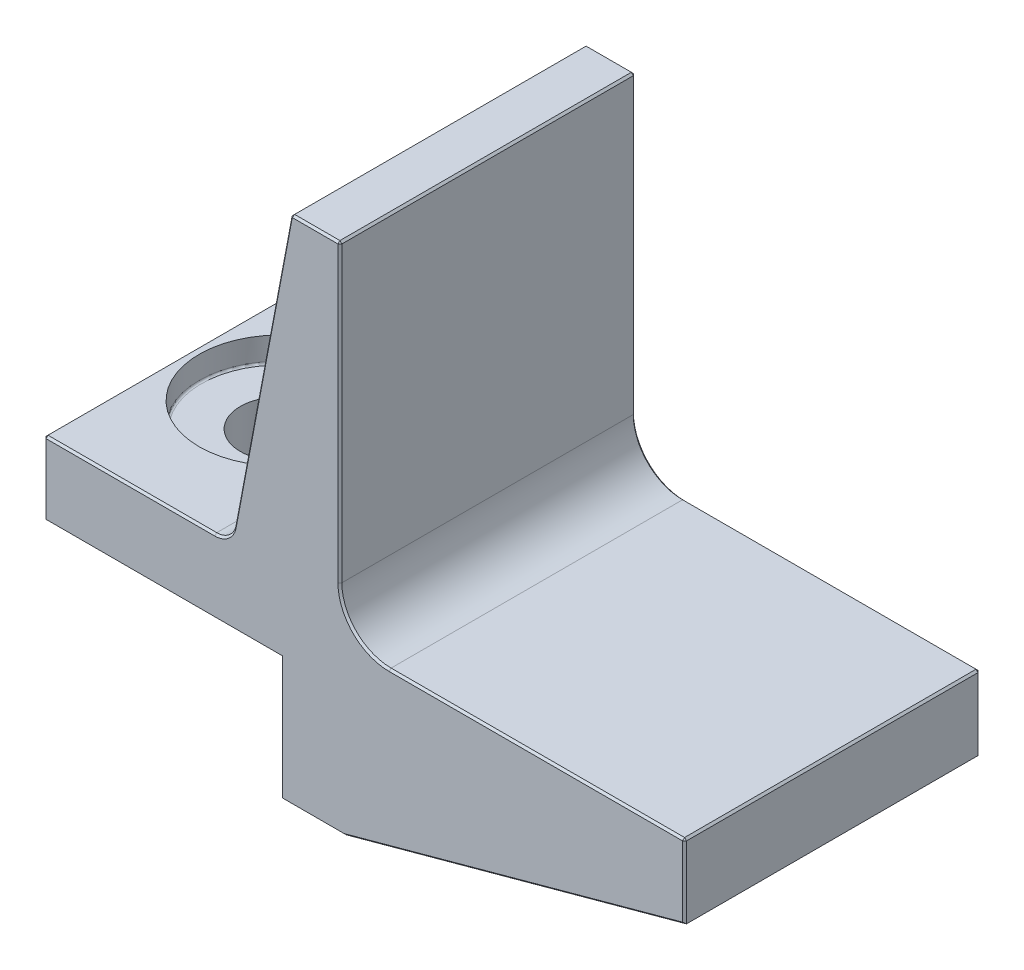
SolidWorks part; units mm, degrees
material "7075-T6 (SN)"
ref_plane "Front Plane" through (0, 0, 0) normal (0, 0, 1) x (1, 0, 0)
ref_plane "Top Plane" through (0, 0, 0) normal (0, 1, 0) x (1, 0, 0)
ref_plane "Right Plane" through (0, 0, 0) normal (1, 0, 0) x (0, 0, -1)
sketch "Sketch1" plane through (0, 0, 0) normal (0, 0, 1) x (1, 0, 0)
  line L0 (0, 0) -> (44.45, 0)
  line L1 (44.45, 0) -> (44.45, -9.525)
  line L2 (-7.6808, -5.6421) -> (-38.1608, -5.6421)
  line L3 (-38.1608, -5.6421) -> (-38.1608, 3.8829)
  line L4 (-38.1608, 3.8829) -> (-14.0308, 3.8829)
  line L5 (-14.0308, 3.8829) -> (-6.35, 44.45)
  line L6 (-6.35, 44.45) -> (0, 44.45)
  line L7 (0, 44.45) -> (0, 0)
  line L8 (-7.6808, -5.6421) -> (-7.6808, -21.5171)
  line L9 (-7.6808, -21.5171) -> (0.5742, -21.5171)
  line L10 (0.5742, -21.5171) -> (44.45, -9.525)
  dimension "D1" = 44.45
  dimension "D2" = 44.45
  dimension "D3" = 9.525
  dimension "D4" = 38.1608
  dimension "D5" = 6.35
  dimension "D6" = 24.13
  dimension "D7" = 30.48
  dimension "D8" = 9.525
  dimension "D9" = 15.875
  dimension "D10" = 8.255
  dimension "D11" = 3.8829
extrude "Boss-Extrude1" add sketch "Sketch1" along normal blind 38.1
hole_wizard "CBORE for 3/8 Binding Head Machine Screw1" positions "Sketch6" profile "Sketch3" counterbore size "3/8" standard "ANSI Inch" end condition through all
sketch "Sketch6" plane through (0, 3.8829, 0) normal (0, 1, 0) x (1, 0, 0)
  line L1 (-38.1608, -38.1) -> (-38.1608, 0) construction
  point P0 (-26.8578, -19.05)
  point P8 (-38.1608, -19.05)
  dimension "D1" = 11.303
sketch "Sketch3" plane through (-26.8578, 3.8829, 19.05) normal (1, 0, 0) x (0, 0, 1)
  line L0 (0, 0) -> (0, 25.4)
  line L1 (0, 25.4) -> (5.0419, 25.4)
  line L3 (5.0419, 25.4) -> (5.0419, 3.175)
  line L4 (10.3378, 3.175) -> (5.0419, 3.175)
  line L5 (10.3378, 3.175) -> (10.3378, 0)
  line L7 (10.3378, 0) -> (0, 0)
  line L11 (0, 0) -> (0, 107.95) construction
  dimension "Thru Hole Dia." = 10.0838
  dimension "Thru Hole Depth" = 25.4
  dimension "C'Bore Depth" = 3.175
fillet "Fillet1" radius 2.54 1 edges at (-14.0308, 3.8829, 19.05)
fillet "Fillet2" radius 6.35 1 edges at (0, 0, 19.05)
chamfer "Chamfer1" distance 0.254 angle 45 31 edges at (-6.35, 44.45, 19.05) (-3.175, 44.45, 0) (-9.9947, 25.2002, 0) (-14.5146, 4.4669, 0) (-27.1479, 3.8829, 0) (-38.1608, -0.8796, 0) (-22.9208, -5.6421, 0) (44.45, -4.7625, 0) (25.4, 0, 0) (1.8599, 1.8599, 0) (0, 25.4, 0) (44.45, -4.7625, 38.1) (-22.9208, -5.6421, 38.1) (-38.1608, -5.6421, 19.05) (-38.1608, -0.8796, 38.1) (-38.1608, 3.8829, 19.05) (-27.1479, 3.8829, 38.1) (-14.5146, 4.4669, 38.1) (-9.9947, 25.2002, 38.1) (-3.175, 44.45, 38.1) (0, 44.45, 19.05) (0, 25.4, 38.1) (1.8599, 1.8599, 38.1) (25.4, 0, 38.1) (44.45, 0, 19.05) (-7.6808, -13.5796, 0) (-3.5533, -21.5171, 0) (22.5121, -15.5211, 0) (22.5121, -15.5211, 38.1) (-3.5533, -21.5171, 38.1) (-7.6808, -13.5796, 38.1) first distance on face at (-3.175, 44.45, 19.05) first distance on face at (-9.9947, 25.2002, 19.05) first distance on face at (-14.7009, 4.6918, 19.05) first distance on face at (-26.8578, 3.8829, 29.3878) first distance on face at (-38.1608, -0.8796, 19.05) first distance on face at (-31.8997, -5.6421, 19.05) first distance on face at (44.45, -4.7625, 19.05) first distance on face at (-2.5328, 3.3352, 0) first distance on face at (2.5174, 2.5174, 19.05) first distance on face at (0, 25.4, 19.05) first distance on face at (-2.5328, 3.3352, 38.1) first distance on face at (-7.6808, -13.5796, 19.05) first distance on face at (-3.5533, -21.5171, 19.05) first distance on face at (22.5121, -15.5211, 19.05)
fillet "Fillet3" radius 0.254 1 edges at (-26.8578, 0.7079, 29.3878)
chamfer "Chamfer2" distance 0.254 angle 45 1 edges at (-31.8997, -5.6421, 19.05)
